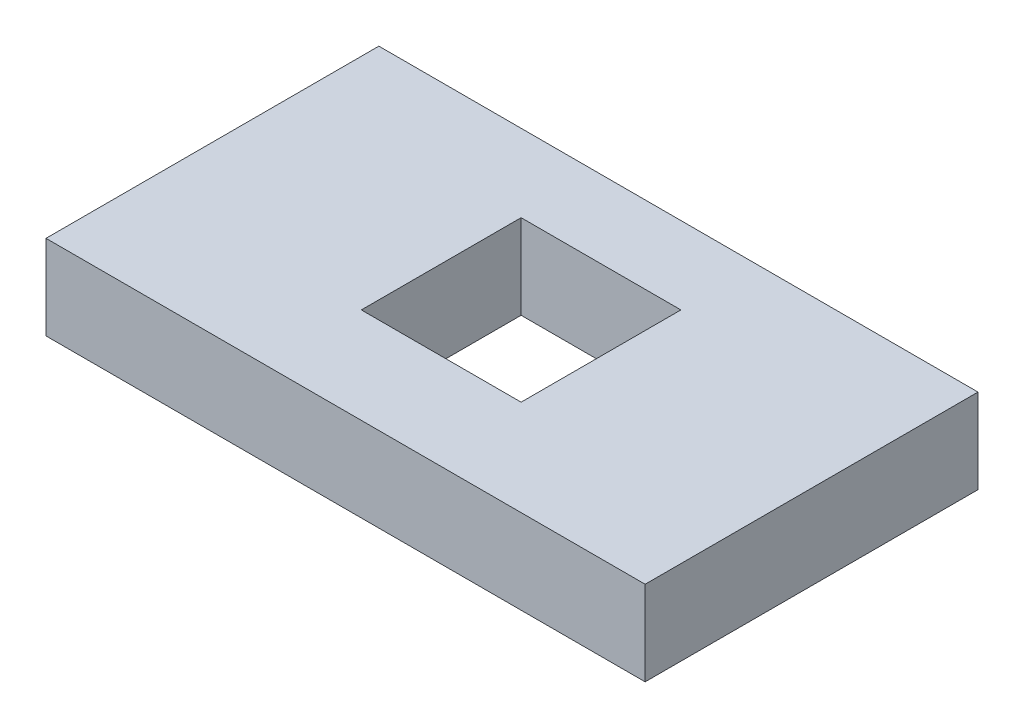
SolidWorks part; units mm, degrees
ref_plane "Front Plane" through (0, 0, 0) normal (0, 0, 1) x (1, 0, 0)
ref_plane "Top Plane" through (0, 0, 0) normal (0, 1, 0) x (1, 0, 0)
ref_plane "Right Plane" through (0, 0, 0) normal (1, 0, 0) x (0, 0, -1)
sketch "Sketch1" plane through (0, 0, 0) normal (0, 1, 0) x (1, 0, 0)
  line L1 (0, 0) -> (45, 0)
  line L2 (0, 0) -> (0, 25)
  line L3 (0, 25) -> (45, 25)
  line L4 (45, 0) -> (45, 25)
  dimension "D1" = 45
  dimension "D2" = 25
extrude "Boss-Extrude1" add sketch "Sketch1" along normal blind 6.35
sketch "Sketch2" plane through (0, 0, 0) normal (0, -1, 0) x (1, 0, 0)
  line L1 (16.5, -19.1848) -> (28.5, -19.1848)
  line L2 (16.5, -19.1848) -> (16.5, -7.1848)
  line L3 (16.5, -7.1848) -> (28.5, -7.1848)
  line L4 (28.5, -19.1848) -> (28.5, -7.1848)
  line L5 (45, 0) -> (45, -25) construction
  dimension "D1" = 12
  dimension "D2" = 12
  dimension "D3" = 16.5
extrude "Cut-Extrude1" cut sketch "Sketch2" against normal through all
